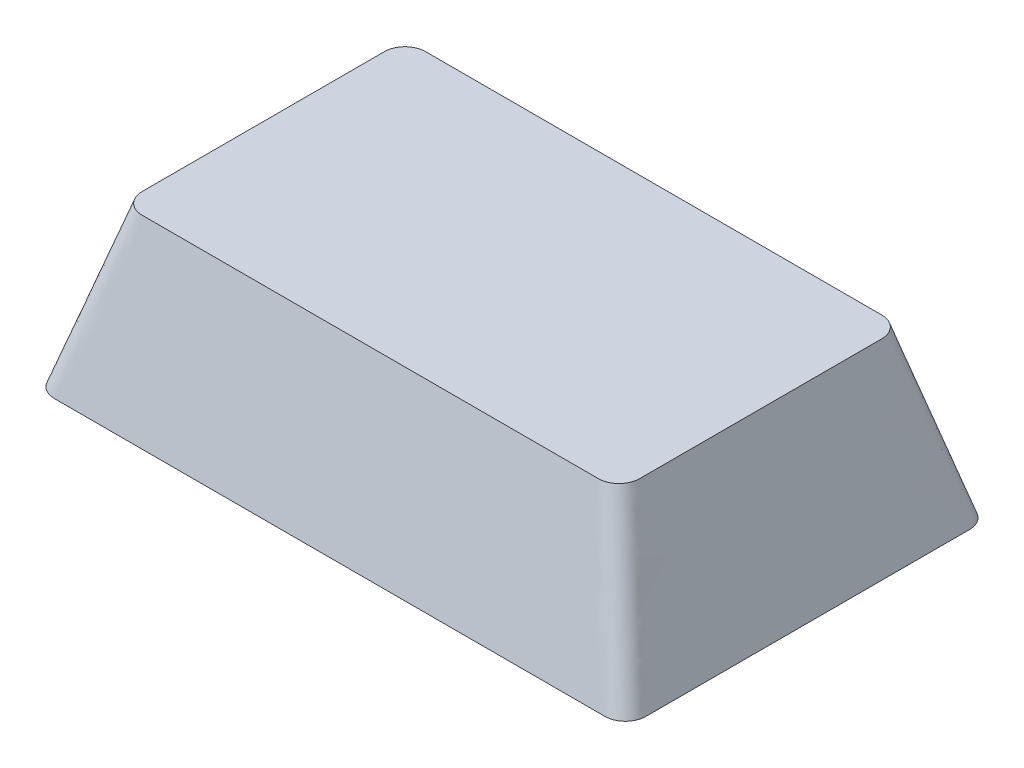
SolidWorks part; units mm, degrees
ref_plane "Alzado" through (0, 0, 0) normal (0, 0, 1) x (1, 0, 0)
ref_plane "Planta" through (0, 0, 0) normal (0, 1, 0) x (1, 0, 0)
ref_plane "Vista lateral" through (0, 0, 0) normal (1, 0, 0) x (0, 0, -1)
sketch "Croquis2" plane through (0, 0, 0) normal (0, 1, 0) x (1, 0, 0)
  line L1 (-13.589, -9.0043) -> (13.589, -9.0043)
  line L2 (-14.605, -7.9883) -> (-14.605, 7.9883)
  line L3 (-13.589, 9.0043) -> (13.589, 9.0043)
  line L4 (14.605, -7.9883) -> (14.605, 7.9883)
  arc A0 (-14.605, 7.9883) -> (-13.589, 9.0043) centre (-13.589, 7.9883) cw
  arc A1 (-13.589, -9.0043) -> (-14.605, -7.9883) centre (-13.589, -7.9883) cw
  arc A2 (13.589, -9.0043) -> (14.605, -7.9883) centre (13.589, -7.9883) ccw
  arc A3 (13.589, 9.0043) -> (14.605, 7.9883) centre (13.589, 7.9883) cw
  point P4 (14.605, 0)
  point P6 (0, 9.0043)
  dimension "D3" = 1.016
  dimension "D1" = 29.21
  dimension "D2" = 18.0086
ref_plane "Plano1" through (0, 8.001, 0) normal (0, 1, 0) x (1, 0, 0)
sketch "Croquis3" plane through (0, 8.001, 0) normal (0, 1, 0) x (1, 0, 0)
  line L1 (-11.2649, -6.9977) -> (11.2649, -6.9977)
  line L2 (-12.2809, -5.9817) -> (-12.2809, 5.9817)
  line L3 (-11.2649, 6.9977) -> (11.2649, 6.9977)
  line L4 (12.2809, -5.9817) -> (12.2809, 5.9817)
  line L5 (-12.2809, -6.9977) -> (12.2809, 6.9977) construction
  line L6 (-12.2809, 6.9977) -> (12.2809, -6.9977) construction
  arc A0 (11.2649, 6.9977) -> (12.2809, 5.9817) centre (11.2649, 5.9817) cw
  arc A1 (11.2649, -6.9977) -> (12.2809, -5.9817) centre (11.2649, -5.9817) ccw
  arc A2 (-11.2649, -6.9977) -> (-12.2809, -5.9817) centre (-11.2649, -5.9817) cw
  arc A3 (-12.2809, 5.9817) -> (-11.2649, 6.9977) centre (-11.2649, 5.9817) cw
  point P0 (0, 0)
  dimension "D3" = 1.016
  dimension "D1" = 24.5618
  dimension "D2" = 13.9954
loft "Recubrir1" add profiles "Croquis3", "Croquis2"
